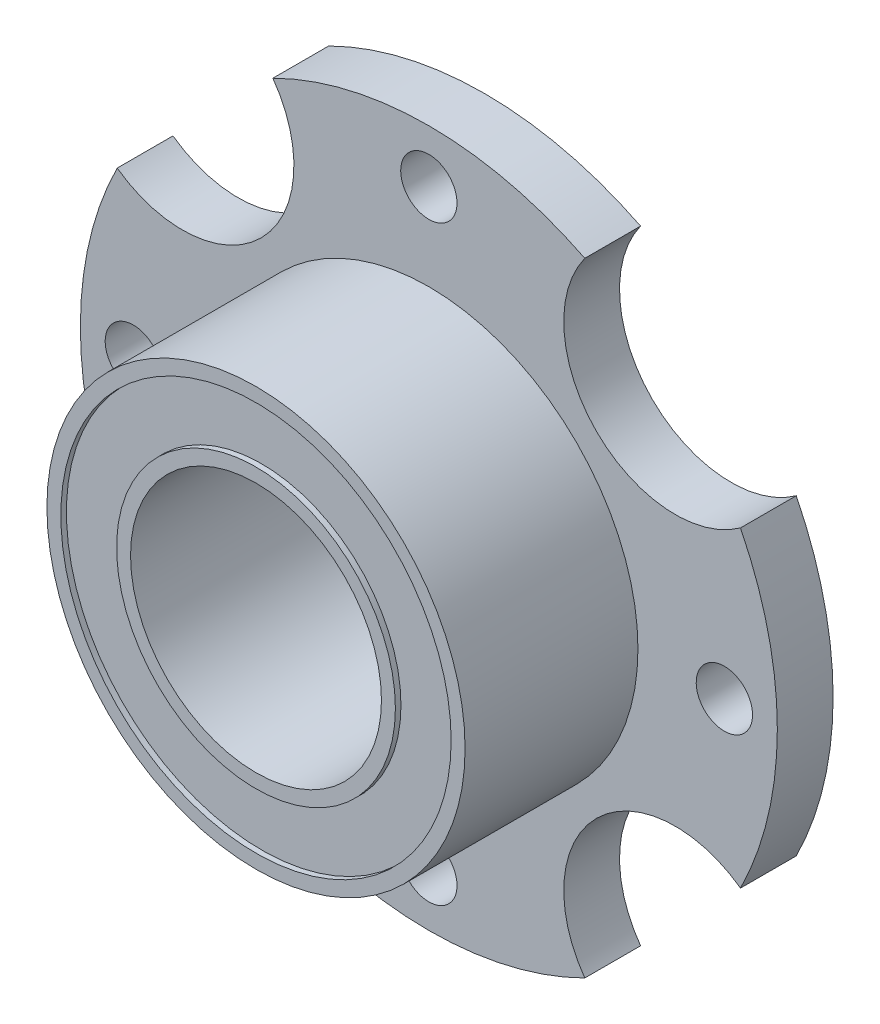
SolidWorks part; units mm, degrees
ref_plane "Płaszczyzna przednia" through (0, 0, 0) normal (0, 0, 1) x (1, 0, 0)
ref_plane "Płaszczyzna górna" through (0, 0, 0) normal (0, 1, 0) x (1, 0, 0)
ref_plane "Płaszczyzna prawa" through (0, 0, 0) normal (1, 0, 0) x (0, 0, -1)
sketch "Szkic1" plane through (0, 0, 0) normal (0, 0, 1) x (1, 0, 0)
  circle A0 centre (0, 0) radius 22.5
  circle A1 centre (0, 0) radius 37.5
  dimension "D1" = 75
  dimension "D2" = 45
extrude "Dodanie-wyciągnięcie1" add sketch "Szkic1" along normal blind 41
sketch "Szkic2" plane through (0, 0, 41) normal (0, 0, 1) x (1, 0, 0)
  circle A0 centre (0, 0) radius 25
  circle A1 centre (0, 0) radius 35
  dimension "D1" = 70
  dimension "D2" = 50
extrude "Wytnij-wyciągnięcie1" cut sketch "Szkic2" against normal blind 1
ref_plane "Płaszczyzna1" through (0, 0, 20.5) normal (0, 0, 1) x (1, 0, 0)
mirror "Lustro1" about plane through (0, 0, 20.5) normal (0, 0, 1) of "Wytnij-wyciągnięcie1"
sketch "Szkic3" plane through (0, 0, 0) normal (0, 0, 1) x (1, 0, 0)
  line L0 (0, 0) -> (-57.5571, -57.5571) construction
  line L1 (0, 0) -> (0, -75) construction
  circle A0 centre (0, -53) radius 5.05
  circle A1 centre (0, 0) radius 37.5
  circle A2 centre (0, 0) radius 37.5 construction
  arc A3 (-27.9715, -55.8914) -> (-55.8914, -27.9715) centre (0, 0) ccw
  arc A4 (-27.9715, -55.8914) -> (-55.8914, -27.9715) centre (-44.1942, -44.1942) ccw
  point P12 (-44.1942, -44.1942)
  dimension "D1" = 10.1
  dimension "D3" = 125
  dimension "D5" = 40
  dimension "D2" = 53
  dimension "D4" = 45
  dimension "D6" = 62.5
extrude "Dodanie-wyciągnięcie2" add sketch "Szkic3" along normal blind 10
pattern_circular "Szyk kołowy1" count 4 every 90 about axis through (0, 0, 41) along (0, 0, 1) of face at (-35.9917, -35.9917, 5) of face at (5.05, -53, 10)
